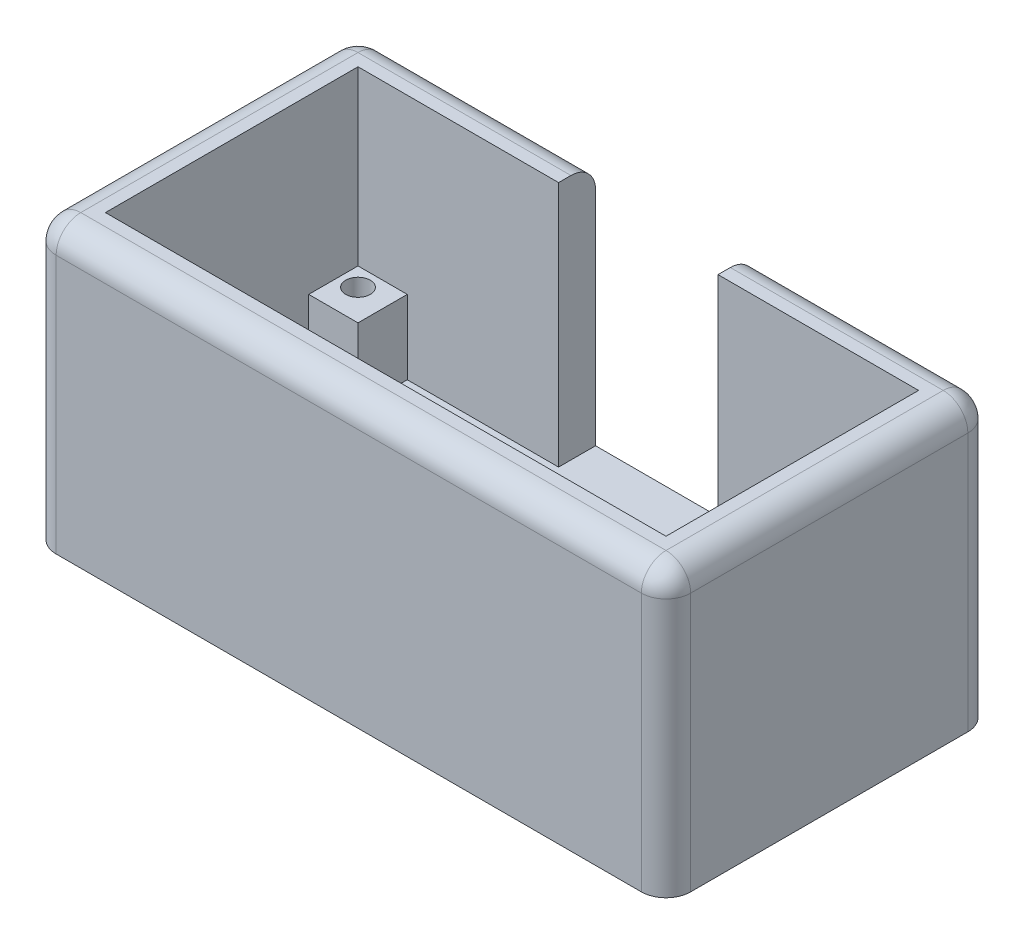
SolidWorks part; units mm, degrees
ref_plane "Спереди" through (0, 0, 0) normal (0, 0, 1) x (1, 0, 0)
ref_plane "Сверху" through (0, 0, 0) normal (0, 1, 0) x (1, 0, 0)
ref_plane "Справа" through (0, 0, 0) normal (1, 0, 0) x (0, 0, -1)
sketch "Эскиз1" plane through (0, 0, 0) normal (0, 1, 0) x (1, 0, 0)
  line L0 (-23, 0.25) -> (15.1596, 0.25) construction
  line L1 (-23, 10.5) -> (22.5, 10.5)
  line L2 (-23, 10.5) -> (-23, -10)
  line L3 (-23, -10) -> (22.5, -10)
  line L4 (22.5, 10.5) -> (22.5, -10)
  line L5 (18.5, -6) -> (22.5, -6)
  line L6 (18.5, 10.5) -> (18.5, 6.5)
  line L7 (18.5, -10) -> (18.5, -6)
  line L8 (-0.25, 0) -> (-0.25, 7.045) construction
  line L9 (-0.25, 10.5) -> (-0.25, 0) construction
  line L10 (22.5, 10.5) -> (20.212, 8.3843) construction
  line L11 (-19, -10) -> (-19, -6)
  line L12 (-19, 10.5) -> (-23, 10.5)
  line L13 (6.2185, 10.5) -> (6.2185, 20.0274)
  line L14 (6.2185, 20.0274) -> (-6.7185, 20.0274)
  line L15 (-6.7185, 10.5) -> (-6.7185, 20.0274)
  line L16 (-0.25, 10.5) -> (-6.7185, 20.0274) construction
  line L17 (6.2185, 20.0274) -> (-0.25, 10.5) construction
  line L18 (-19, 10.5) -> (-19, 6.5)
  line L19 (-19, 6.5) -> (-23, 6.5)
  line L20 (-23, 10.5) -> (-23, 6.5)
  line L21 (-19, -6) -> (-23, -6)
  line L23 (18.5, 6.5) -> (22.5, 6.5)
  line L24 (-26, 13.5) -> (25.5, 13.5)
  line L25 (-26, 13.5) -> (-26, -13)
  line L26 (-26, -13) -> (25.5, -13)
  line L27 (25.5, 13.5) -> (25.5, -13)
  line L28 (-26, 13.5) -> (25.5, -13) construction
  line L29 (-26, -13) -> (25.5, 13.5) construction
  circle A0 centre (-21.5, 9) radius 1
  circle A1 centre (21, 9) radius 1
  circle A2 centre (21, -8.5) radius 1
  circle A3 centre (-21.5, -8.5) radius 1
  point P0 (0, 0)
  point P41 (-0.25, 0.25)
  dimension "D3" = 1.5
  dimension "D4" = 4
  dimension "D1" = 45.5
  dimension "D2" = 20.5
  dimension "D5" = 4
  dimension "D6" = 3
  dimension "D7" = 3
  dimension "D8" = 3
  dimension "D9" = 3
  dimension "D10" = 1.5
  dimension "D11" = 1.5
  dimension "D12" = 1.5
  dimension "D13" = 1.5
  dimension "D14" = 1.5
extrude "Бобышка-Вытянуть1" add sketch "Эскиз1" along normal blind 20 contours L27 L24 L13 L1 L4 L3 L2 L15 L25 L26 region at (-23.5792, 0, -8.5)
extrude "Бобышка-Вытянуть2" add sketch "Эскиз1<3>" along normal blind 6 contours L19 L18 L1 L2 A0 | L6 L23 L4 L1 A1 | L7 L3 L4 L5 A2 | L11 L21 L2 L3 A3 region at (-21, 0, -10.4434) region at (-21, 0, 6.0566) region at (20.5, 0, -10.4434) region at (18.5566, 0, 8)
sketch "Эскиз1<3>" plane through (0, 0, 0) normal (0, 1, 0) x (1, 0, 0) same geometry as "Эскиз1"
extrude "Бобышка-Вытянуть3" add sketch "Эскиз1<4>" against normal blind 3 contours L27 L24 L13 L1 L4 L3 L2 L15 L25 L26 | L23 L6 L1 L18 L19 L2 L21 L11 L3 L7 L5 L4 | L7 L3 L4 L5 A2 | L6 L23 L4 L1 A1 | A3 | L11 L21 L2 L3 A3 | L19 L18 L1 L2 A0 | A0 | A1 | A2 | L24 L15 L1 L13 region at (-23.5792, 0, -8.5) region at (-21, 0, -10.4434) region at (-0.25, 0, -0.25) region at (-0.25, 0, -12) region at (-21, 0, 6.0566) region at (20.5, 0, -10.4434) region at (18.5566, 0, 8) region at (-21.5, 0, -9) region at (21, 0, -9) region at (21, 0, 8.5) region at (-21.5, 0, 8.5)
sketch "Эскиз1<4>" plane through (0, 0, 0) normal (0, 1, 0) x (1, 0, 0) same geometry as "Эскиз1"
fillet "Скругление1" radius 2 9 edges at (-26, 20, -0.25) (-16.3593, 20, -13.5) (15.8593, 20, -13.5) (25.5, 20, -0.25) (-0.25, 20, 13) (-26, 8.5, 13) (-26, 8.5, -13.5) (25.5, 8.5, -13.5) (25.5, 8.5, 13)
sketch "Эскиз3" plane through (0, -3, 0) normal (0, -1, 0) x (1, 0, 0)
  line L0 (0, 0) -> (0, 43.8421) construction
  line L1 (-24, 13) -> (23.5, 13) construction
  line L2 (2.5, 43) -> (-2.5, 43)
  line L3 (0, 43) -> (0, 43.8421)
  line L4 (2.5, 13) -> (-2.5, 13)
  line L5 (-2.5, 43) -> (-2.5, 13)
  line L6 (0, 43) -> (-2.5, 13) construction
  line L7 (0, 13) -> (-2.5, 43) construction
  line L8 (2.5, 43) -> (2.5, 13)
  point P7 (-1.25, 28)
  dimension "D1" = 30
  dimension "D2" = 2.5
